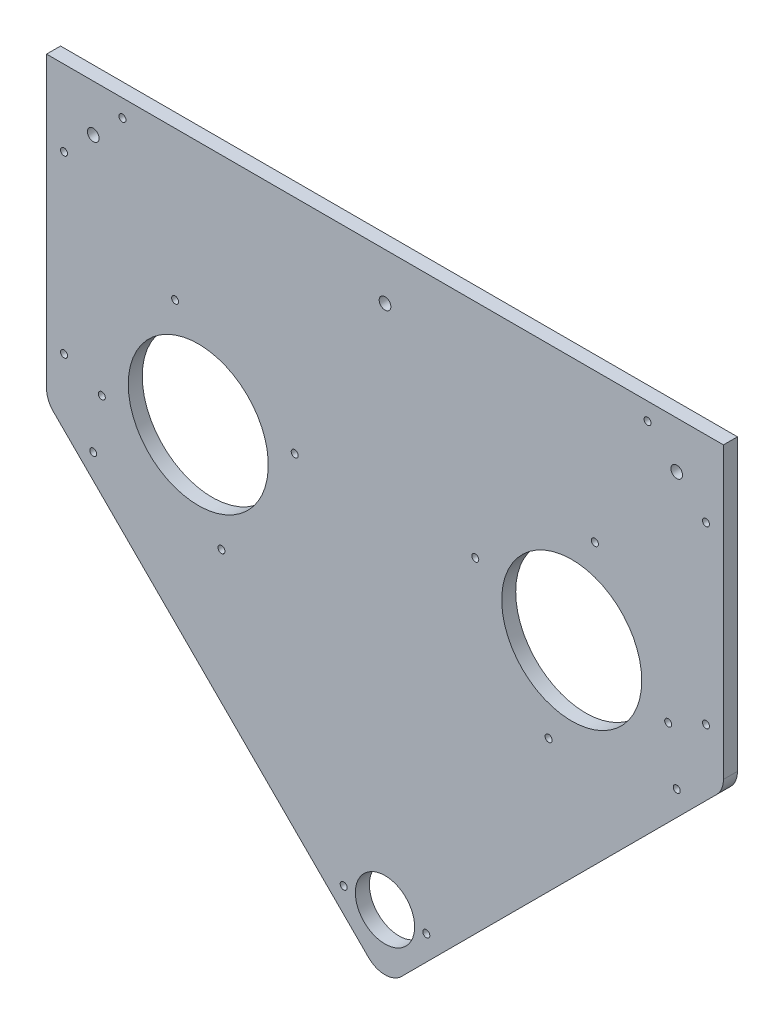
SolidWorks part; units mm, degrees
ref_plane "Front Plane" through (0, 0, 0) normal (0, 0, 1) x (1, 0, 0)
ref_plane "Top Plane" through (0, 0, 0) normal (0, 1, 0) x (1, 0, 0)
ref_plane "Right Plane" through (0, 0, 0) normal (1, 0, 0) x (0, 0, -1)
sketch "Sketch1" plane through (0, 0, 0) normal (0, 0, 1) x (1, 0, 0)
  line L0 (-125, 100) -> (125, 100) construction
  line L1 (-125, 0) -> (125, 0) construction
  line L2 (-137.5158, 87.4842) -> (-125, 100) construction
  line L3 (0, -125) -> (-125, 0) construction
  line L4 (0, -125) -> (-17.7, -125) construction
  line L5 (-125, -17.7) -> (-125, 0) construction
  line L6 (0, -125) -> (0, 100) construction
  line L7 (-145, 120) -> (145, 120)
  line L8 (145, 120) -> (145, -8.2843)
  line L9 (145, -8.2843) -> (0, -153.2843)
  line L10 (0, -153.2843) -> (-145, -8.2843)
  line L11 (-145, -8.2843) -> (-145, 120)
  circle A0 centre (-125, 100) radius 12.7 construction
  circle A1 centre (125, 100) radius 12.7 construction
  circle A4 centre (0, -125) radius 12.7
  circle A5 centre (-137.5158, 87.4842) radius 1.5
  circle A6 centre (-112.4842, 112.5158) radius 1.5
  circle A7 centre (-137.5158, 12.5158) radius 1.5
  circle A8 centre (-125, -17.7) radius 1.5
  circle A9 centre (-17.7, -125) radius 1.5
  circle A10 centre (-125, 0) radius 12.7 construction
  circle A11 centre (125, 0) radius 12.7 construction
  circle A12 centre (-125, 0) radius 17.7 construction
  circle A13 centre (-125, 100) radius 17.7 construction
  circle A14 centre (0, -125) radius 17.7 construction
  circle A15 centre (17.7, -125) radius 1.5
  circle A16 centre (125, -17.7) radius 1.5
  circle A17 centre (137.5158, 12.5158) radius 1.5
  circle A18 centre (137.5158, 87.4842) radius 1.5
  circle A19 centre (112.4842, 112.5158) radius 1.5
  circle A20 centre (0, 100) radius 2.5
  circle A21 centre (-125, 100) radius 2.5
  circle A22 centre (125, 100) radius 2.5
  point P12 (0, 100)
  point P45 (0, 120)
  dimension "D1" = 25.4
  dimension "D5" = 3
  dimension "D2" = 5
  dimension "D4" = 100
  dimension "D6" = 5
  dimension "D7" = 135
  dimension "D8" = 45
  dimension "D9" = 250
  dimension "D10" = 45
  dimension "D11" = 20
  dimension "D12" = 20
  dimension "D13" = 20
  dimension "D14" = 20
  dimension "D15" = 20
  dimension "D3" = 125
extrude "Boss-Extrude1" add sketch "Sketch1" along normal blind 6
fillet "Fillet1" radius 10 3 edges at (-145, -8.2843, 3) (145, -8.2843, 3) (0, -153.2843, 3)
sketch "Sketch2" plane through (0, 0, 6) normal (0, 0, 1) x (1, 0, 0)
  line L0 (121.326, 5.0796) -> (38.674, 24.9204) construction
  line L1 (70.0796, -26.326) -> (89.9204, 56.326) construction
  line L2 (0, 0) -> (0, 100) construction
  line L3 (145, 120) -> (-145, 120) construction
  line L4 (-145, 120) -> (-145, -4.1421) construction
  circle A0 centre (80, 15) radius 42.5 construction
  circle A1 centre (38.674, 24.9204) radius 1.5
  circle A2 centre (89.9204, 56.326) radius 1.5
  circle A3 centre (121.326, 5.0796) radius 1.5
  circle A4 centre (70.0796, -26.326) radius 1.5
  circle A5 centre (80, 15) radius 30
  circle A6 centre (-38.674, 24.9204) radius 1.5
  circle A7 centre (-89.9204, 56.326) radius 1.5
  circle A8 centre (-70.0796, -26.326) radius 1.5
  circle A9 centre (-121.326, 5.0796) radius 1.5
  circle A10 centre (-80, 15) radius 42.5 construction
  circle A11 centre (-80, 15) radius 30
  circle A12 centre (-80, 15) radius 47.5 construction
  circle A13 centre (-137.5158, 12.5158) radius 3 construction
  circle A14 centre (-125, -17.7) radius 3 construction
  point P6 (80, 15)
  point P27 (-80, 15)
  point P32 (-81.6259, 12.6627)
  dimension "D1" = 85
  dimension "D2" = 3
  dimension "D3" = 60
  dimension "D4" = 95
  dimension "D5" = 6
  dimension "D6" = 105
  dimension "D7" = 65
extrude "Cut-Extrude1" cut sketch "Sketch2" against normal blind 10
equation "\"carbon_fiber_tube_diam\"= 1in"
equation "\"clip_tube_diam\"= 6mm"
equation "\"D1@Sketch1\"=\"carbon_fiber_tube_diam\""
equation "\"middle_tube_len\"= 500mm"
equation "\"horizontal_pipe_spacing\"= 250mm"
equation "\"D9@Sketch1\"=\"horizontal_pipe_spacing\""
